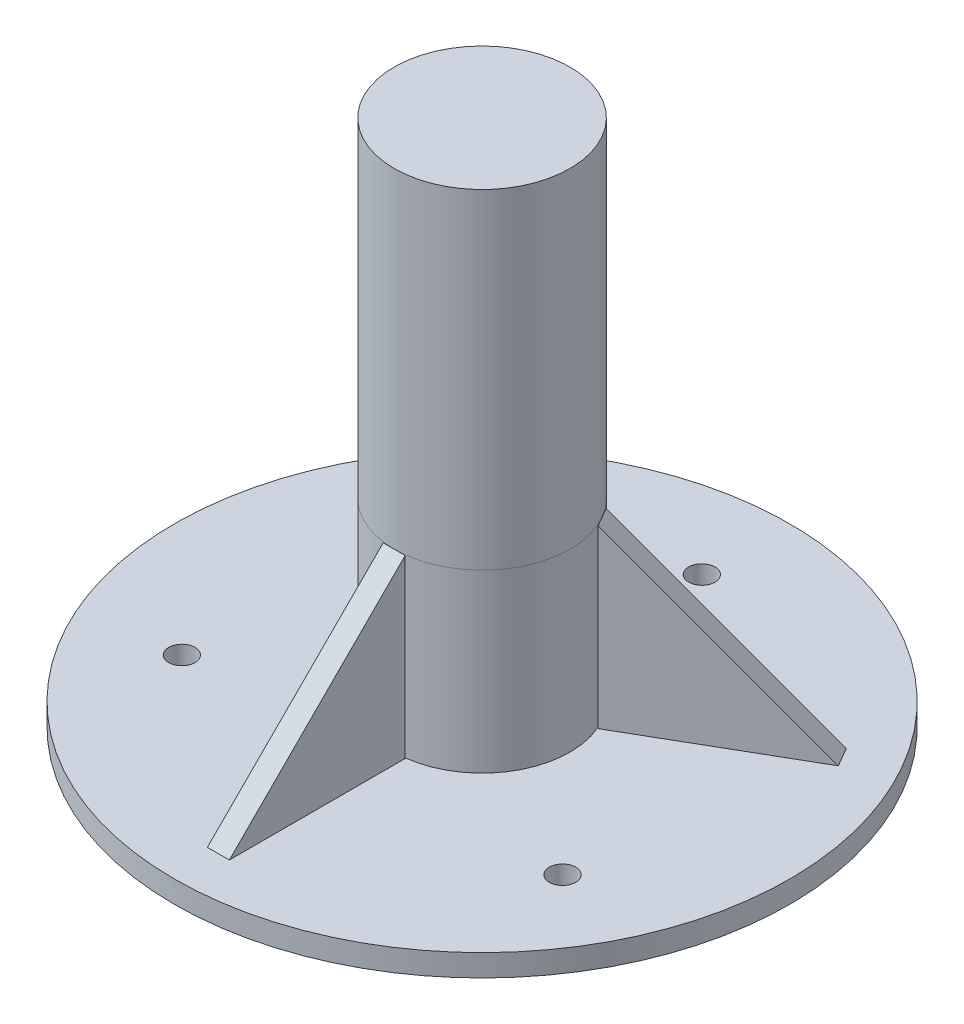
SolidWorks part; units mm, degrees
ref_plane "Front Plane" through (0, 0, 0) normal (0, 0, 1) x (1, 0, 0)
ref_plane "Top Plane" through (0, 0, 0) normal (0, 1, 0) x (1, 0, 0)
ref_plane "Right Plane" through (0, 0, 0) normal (1, 0, 0) x (0, 0, -1)
sketch "Sketch1" plane through (0, 0, 0) normal (0, 1, 0) x (1, 0, 0)
  circle A0 centre (0, 0) radius 70
  dimension "D1" = 140
extrude "Boss-Extrude1" add sketch "Sketch1" against normal blind 5
sketch "Sketch2" plane through (0, 0, 0) normal (0, 1, 0) x (1, 0, 0)
  circle A0 centre (0, 0) radius 20
  dimension "D1" = 40
extrude "Boss-Extrude2" add sketch "Sketch2" along normal blind 40 separate body
sketch "Sketch3" plane through (0, 40, 0) normal (0, 1, 0) x (1, 0, 0)
  circle A0 centre (0, 0) radius 20 construction
  circle A1 centre (0, 0) radius 20
extrude "Boss-Extrude3" add sketch "Sketch3" along normal blind 75 separate body
sketch "Sketch4" plane through (0, 0, 0) normal (1, 0, 0) x (0, 0, -1)
  line L0 (-60, 0) -> (-20, 0)
  line L1 (-20, 0) -> (-20, 40)
  line L2 (-20, 40) -> (-60, 0)
  line L3 (70, 0) -> (-70, 0) construction
  line L4 (-20, 40) -> (-20, 0) construction
  dimension "D1" = 40
  dimension "D2" = 45
  dimension "D3" = 0
  dimension "D4" = 0
extrude "Boss-Extrude4" add sketch "Sketch4" along normal blind 2.5 and the other way blind 2.5 separate body
pattern_circular "CirPattern1" count 3 every 120 about axis through (0, 40, 0) along (0, -1, 0) of "Boss-Extrude4"
sketch "Sketch5" plane through (0, 0, 0) normal (0, 1, 0) x (1, 0, 0)
  line L0 (16.0705, 12.1651) -> (50.7115, 32.1651) construction
  circle A0 centre (-43.3013, -25) radius 3
  circle A1 centre (0, 50) radius 3
  circle A2 centre (43.3013, -25) radius 3
  point P11 (0, 0)
  dimension "D1" = 6
  dimension "D2" = 2.5
  dimension "D3" = 50
  dimension "D4" = 3
extrude "Cut-Extrude1" cut sketch "Sketch5" against normal through all
